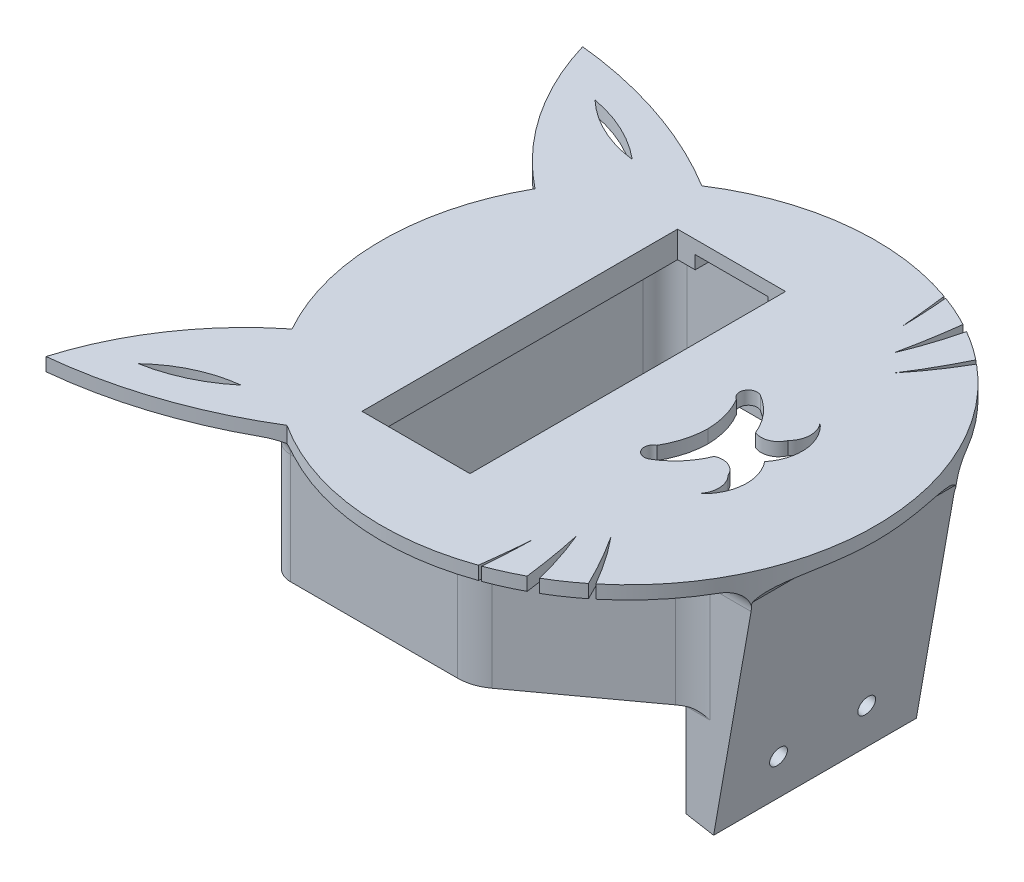
SolidWorks part; units mm, degrees
ref_plane "Front Plane" through (0, 0, 0) normal (0, 0, 1) x (1, 0, 0)
ref_plane "Top Plane" through (0, 0, 0) normal (0, 1, 0) x (1, 0, 0)
ref_plane "Right Plane" through (0, 0, 0) normal (1, 0, 0) x (0, 0, -1)
sketch "Sketch3" plane through (0, 0, 0) normal (0, 1, 0) x (1, 0, 0)
  line L0 (-100, 0) -> (0, 0) construction
  line L2 (-48.8284, -35.8) -> (-24.3284, -35.8)
  line L3 (-48.8284, -35.8) -> (-48.8284, 35.8)
  line L4 (-48.8284, 35.8) -> (-24.3284, 35.8)
  line L5 (-24.3284, -35.8) -> (-24.3284, 35.8)
  line L6 (-48.8284, -35.8) -> (-24.3284, 35.8) construction
  line L7 (-48.8284, 35.8) -> (-24.3284, -35.8) construction
  circle A0 centre (-24.1215, 0) radius 56.0598
  arc A1 (-54.5886, -47.058) -> (-95.4475, -60.8804) centre (-105.4462, 35.9761) cw
  arc A2 (-95.4475, -60.8804) -> (-72.9377, -27.5623) centre (-31.2759, -79.972) cw
  arc A3 (-54.5886, 47.058) -> (-95.4475, 60.8804) centre (-105.4462, -35.9761) ccw
  arc A4 (-95.4475, 60.8804) -> (-72.9377, 27.5623) centre (-31.2759, 79.972) ccw
  arc A5 (-6.1696, 0) -> (-8.7065, 9.0222) centre (-24.4857, -0.2825) ccw
  arc A6 (-8.7065, 9.0222) -> (-6.8513, 12.5893) centre (-7.7789, 10.8058) cw
  arc A7 (-6.8513, 12.5893) -> (0, 4.6761) centre (-15.0294, -1.4138) cw
  arc A8 (0, 4.6761) -> (5.2387, 6.7988) centre (1.558, 8.3568) ccw
  arc A9 (5.2387, 6.7988) -> (5.2387, 14.0413) centre (1.6175, 10.4201) ccw
  arc A10 (5.2387, 14.0413) -> (6.7387, 0) centre (-1.032, 6.2707) cw
  arc A11 (0, -4.6761) -> (5.2387, -6.7988) centre (1.558, -8.3568) cw
  arc A12 (5.2387, -6.7988) -> (5.2387, -14.0413) centre (1.6175, -10.4201) cw
  arc A13 (-6.8513, -12.5893) -> (0, -4.6761) centre (-15.0294, 1.4138) ccw
  arc A14 (-8.7065, -9.0222) -> (-6.8513, -12.5893) centre (-7.7789, -10.8058) ccw
  arc A15 (-6.1696, 0) -> (-8.7065, -9.0222) centre (-24.4857, 0.2825) cw
  arc A16 (5.2387, -14.0413) -> (6.7387, 0) centre (-1.032, -6.2707) ccw
  arc A17 (-4.2521, 42.0799) -> (-18.8641, 106.2073) centre (-236.5807, 22.8701) ccw
  arc A18 (-18.8641, 106.2073) -> (-4.2521, 42.0799) centre (-168.4211, 38.4009) cw
  arc A19 (0, 36) -> (-1.032, 103.0638) centre (-143.6963, 67.3287) ccw
  arc A20 (-1.032, 103.0638) -> (0, 36) centre (-77.2813, 68.3507) cw
  arc A21 (4.0199, 32.1345) -> (21.5381, 91.1561) centre (-86.4358, 91.0932) ccw
  arc A22 (21.5381, 91.1561) -> (4.0199, 32.1345) centre (-57.6041, 82.5357) cw
  arc A23 (4.0199, -32.1345) -> (21.5381, -91.1561) centre (-86.4358, -91.0932) cw
  arc A24 (-1.032, -103.0638) -> (0, -36) centre (-77.2813, -68.3507) ccw
  arc A25 (0, -36) -> (-1.032, -103.0638) centre (-143.6963, -67.3287) cw
  arc A26 (-18.8641, -106.2073) -> (-4.2521, -42.0799) centre (-168.4211, -38.4009) ccw
  arc A27 (-4.2521, -42.0799) -> (-18.8641, -106.2073) centre (-236.5807, -22.8701) cw
  arc A28 (21.5381, -91.1561) -> (4.0199, -32.1345) centre (-57.6041, -82.5357) ccw
  arc A29 (-83.5713, 51.8155) -> (-67.669, 44.359) centre (-89.6943, 18.0714) cw
  arc A30 (-83.5713, 51.8155) -> (-67.669, 44.359) centre (-64.4592, 71.8903) ccw
  arc A31 (-83.5713, -51.8155) -> (-67.669, -44.359) centre (-89.6943, -18.0714) ccw
  arc A32 (-83.5713, -51.8155) -> (-67.669, -44.359) centre (-64.4592, -71.8903) cw
  point P3 (-36.5784, 0)
  dimension "D1" = 71.6
  dimension "D2" = 24.5
  dimension "D3" = 100
extrude "Boss-Extrude1" add sketch "Sketch3" along normal blind 3 contours A0 L5 L2 L3 L4 | A3 A4 A0 | A2 A1 A0
sketch "Sketch9" plane through (0, 0, 0) normal (0, -1, 0) x (1, 0, 0)
  line L0 (-48.8284, 35.8) -> (-24.3284, 35.8)
  line L1 (-24.3284, 35.8) -> (-24.3284, -35.8)
  line L2 (-24.3284, -35.8) -> (-28.3284, -35.8)
  line L3 (-48.8284, -35.8) -> (-24.3284, -35.8) construction
  line L4 (-28.3284, -35.8) -> (-28.3284, -40.8)
  line L5 (-28.3284, -40.8) -> (-19.3284, -40.8)
  line L6 (-19.3284, -40.8) -> (-19.3284, 40.8)
  line L7 (-19.3284, 40.8) -> (-53.8284, 40.8)
  line L8 (-53.8284, 40.8) -> (-53.8284, 34.8)
  line L9 (-53.8284, 34.8) -> (-50.8284, 34.8)
  line L10 (-50.8284, 34.8) -> (-50.8284, -10.8)
  line L11 (-50.8284, -10.8) -> (-53.8284, -10.8)
  line L12 (-53.8284, -10.8) -> (-53.8284, -40.8)
  line L13 (-53.8284, -40.8) -> (-44.8284, -40.8)
  line L14 (-44.8284, -40.8) -> (-44.8284, -35.8)
  line L15 (-44.8284, -35.8) -> (-48.8284, -35.8)
  line L16 (-48.8284, -35.8) -> (-48.8284, 35.8)
  line L17 (-24.3284, 35.8) -> (-24.3284, -35.8)
  line M53 (-24.3284, 35.8) -> (-24.3284, -35.8)
  line M54 (-24.3284, -35.8) -> (-48.8284, -35.8)
  line M55 (-48.8284, -35.8) -> (-48.8284, 35.8)
  line M56 (-48.8284, 35.8) -> (-24.3284, 35.8)
  dimension "D1" = 4
  dimension "D2" = 5
  dimension "D3" = 5
  dimension "D4" = 25
  dimension "D5" = 2
  dimension "D6" = 1
  dimension "D7" = 5
extrude "Boss-Extrude2" add sketch "Sketch9" along normal blind 3 contours L13 L14 L4 L5 L6 L7 L8 L9 L10 L11 L12 M54 M55 M56 M53
sketch "Sketch10" plane through (0, 0, 0) normal (0, -1, 0) x (1, 0, 0)
  line L0 (-80.1813, 0) -> (31.9383, 0) construction
  line L3 (-23.9972, -23) -> (27.0028, -23)
  line L4 (-23.9972, -23) -> (-23.9972, 23)
  line L5 (-23.9972, 23) -> (27.0028, 23)
  line L6 (27.0028, -23) -> (27.0028, 23)
  line L7 (-23.9972, -23) -> (27.0028, 23) construction
  line L8 (-23.9972, 23) -> (27.0028, -23) construction
  line L9 (-10.9312, -14.4635) -> (13.9368, -14.4635)
  line L10 (-10.9312, -14.4635) -> (-10.9312, 14.4635)
  line L11 (-10.9312, 14.4635) -> (13.9368, 14.4635)
  line L12 (13.9368, -14.4635) -> (13.9368, 14.4635)
  line L13 (-10.9312, -14.4635) -> (13.9368, 14.4635) construction
  line L14 (-10.9312, 14.4635) -> (13.9368, -14.4635) construction
  arc A0 (-72.9377, 27.5623) -> (-72.9377, -27.5623) centre (-24.1215, 0) ccw construction
  arc A1 (11.6083, -43.1981) -> (11.6083, 43.1981) centre (-24.1215, 0) ccw construction
  point P9 (1.5028, 0)
  point P10 (1.5028, 0)
  dimension "D1" = 46
  dimension "D2" = 51
extrude "Boss-Extrude3" add sketch "Sketch10" along normal blind 3
ref_plane "Plane1" through (26.7016, -4.7082, 0) normal (0.9848, -0.1736, 0) x (0, 0, 1)
sketch "Sketch11" plane through (26.7016, -4.7082, 0) normal (0.9848, -0.1736, 0) x (0, 0, 1)
  line L0 (-23, -1.7346) -> (23, -1.7346)
  line L1 (23, -1.7346) -> (23, 49.2654)
  line L2 (23, 49.2654) -> (-23, 49.2654)
  line L3 (-23, 49.2654) -> (-23, -1.7346)
  line L4 (0, 48.4772) -> (0, -1.7346) construction
  circle A0 centre (-10, 39.2654) radius 2
  circle A1 centre (10, 39.2654) radius 2
  dimension "D2" = 4
  dimension "D1" = 51
  dimension "D3" = 10
  dimension "D4" = 10
extrude "Boss-Extrude4" add sketch "Sketch11" against normal blind 5
sketch "Sketch13" plane through (0, -3, 0) normal (0, -1, 0) x (1, 0, 0)
  line L0 (13.9368, 14.4635) -> (13.9368, 23)
  line L1 (21.9257, 23) -> (-19.3284, 23) construction
  line L2 (13.9368, 23) -> (21.9257, 23)
  line L3 (21.9257, 23) -> (21.9257, -23)
  line L4 (21.9257, -23) -> (21.9257, 23) construction
  line L5 (21.9257, -23) -> (13.9368, -23)
  line L6 (-19.3284, -23) -> (21.9257, -23) construction
  line L7 (13.9368, -23) -> (13.9368, -14.4635)
  line L8 (13.9368, -14.4635) -> (13.9368, 14.4635)
extrude "Boss-Extrude5" add sketch "Sketch13" along normal blind 27
sketch "Sketch16" plane through (0, -30, 0) normal (0, -1, 0) x (1, 0, 0)
  line L0 (17.1649, 23) -> (13.9368, 23)
  line L1 (13.9368, 23) -> (13.9368, -23)
  line L2 (13.9368, -23) -> (17.1649, -23)
  line L3 (17.1649, -23) -> (17.1649, 23.2709)
  line M1 (13.9368, -23) -> (17.1649, -23)
  line M2 (17.1649, -23) -> (17.1649, 23)
  line M3 (17.1649, 23) -> (13.9368, 23)
  line M4 (13.9368, 23) -> (13.9368, -23)
extrude "Boss-Extrude6" [suppressed] add sketch "Sketch16" along normal blind 9 draft 10 contours M4 M1 M2 M3
sketch "Sketch17" plane through (0, 0, 0) normal (0, -1, 0) x (1, 0, 0)
  line L0 (-80.1813, 0) -> (31.9383, 0) construction
  line L2 (-19.4509, -40.8) -> (-56.6775, -40.8)
  line L3 (-28.3284, -40.8) -> (-19.3284, -40.8) construction
  line L4 (-56.6775, -40.8) -> (-56.6775, 40.8)
  line L5 (-56.6775, 0) -> (-73.3467, 0)
  line L6 (-73.3467, 0) -> (-60.1571, -44.4025)
  line L7 (-60.1571, -44.4025) -> (-15.3287, -44.4025)
  line L8 (-15.3287, -44.4025) -> (14.0672, -23)
  line L9 (-19.3284, -23) -> (27.0028, -23) construction
  line L10 (14.0672, -23) -> (-15.3287, -23)
  line L11 (-15.3287, -23) -> (-15.3287, -40.8)
  line L12 (-15.3287, -40.8) -> (-19.4509, -40.8)
  line L13 (-56.6775, -40.8) -> (-19.4509, -40.8)
  line L14 (-15.3287, -23) -> (14.0672, -23)
  line L15 (-19.4509, 40.8) -> (-56.6775, 40.8)
  line L16 (-15.3287, 40.8) -> (-19.4509, 40.8)
  line L17 (-15.3287, 23) -> (-15.3287, 40.8)
  line L18 (14.0672, 23) -> (-15.3287, 23)
  line L19 (-15.3287, 44.4025) -> (14.0672, 23)
  line L20 (-60.1571, 44.4025) -> (-15.3287, 44.4025)
  line L21 (-73.3467, 0) -> (-60.1571, 44.4025)
  arc A0 (-72.9377, 27.5623) -> (-72.9377, -27.5623) centre (-24.1215, 0) ccw construction
  arc A1 (27.0028, -23) -> (27.0028, 23) centre (-24.1215, 0) ccw construction
  line M14 (-19.3284, 23) -> (27.0028, 23)
  line M40 (27.0028, -23) -> (-19.3284, -23)
  line M42 (-19.3284, -40.8) -> (-28.3284, -40.8)
  line M46 (-44.8284, -40.8) -> (-53.8284, -40.8)
  line M52 (-53.8284, 40.8) -> (-19.3284, 40.8)
extrude "Boss-Extrude7" add sketch "Sketch17" along normal blind 30 contours L11 L12 L2 L4 L5 L6 L7 L8 M42 M46 M40 | L21 L5 L4 L15 L16 L17 L19 L20 M52 M14
fillet "Fillet4" radius 20 1 edges at (-73.3467, -15, 0)
fillet "Fillet5" radius 5 2 edges at (-60.1571, -15, -44.4025) (-60.1571, -15, 44.4025)
fillet "Fillet6" radius 10 2 edges at (-15.3287, -15, 44.4025) (-15.3287, -15, -44.4025)
sketch "Sketch24" [suppressed] plane through (21.7776, -3.84, 0) normal (-0.9848, 0.1736, 0) x (0, 0, 1)
  line L0 (23, -49.2654) -> (-23, -49.2654)
  line L1 (-23, -49.2654) -> (-23, -26.5636)
  line L2 (-23, -26.5636) -> (23, -26.5636)
  line L3 (23, -26.5636) -> (23, -49.2654)
sketch "Sketch25" plane through (0, -30, 0) normal (0, -1, 0) x (1, 0, 0)
sketch "Sketch46" plane through (0, -30, 0) normal (0, -1, 0) x (1, 0, 0)
  line L0 (17.1649, -23) -> (17.1649, 23)
  line L1 (17.1649, 23) -> (15.6649, 23)
  line L2 (17.1649, 23) -> (14.0672, 23) construction
  line L3 (15.6649, 23) -> (15.6649, -23)
  line L4 (14.0672, -23) -> (17.1649, -23) construction
  line L5 (15.6649, -23) -> (17.1649, -23)
  dimension "D1" = 1.5
extrude "Boss-Extrude10" add sketch "Sketch46" along normal up to surface (8.5069 mm away)
sketch "Sketch47" plane through (0, 0, 0) normal (0, -1, 0) x (1, 0, 0)
  line L0 (13.9368, 14.4635) -> (13.9368, -14.4635)
  line L1 (13.9368, -14.4635) -> (11.9368, -14.4635)
  line L2 (-10.9312, -14.4635) -> (13.9368, -14.4635) construction
  line L3 (11.9368, -14.4635) -> (11.9368, 14.4635)
  line L4 (13.9368, 14.4635) -> (-10.9312, 14.4635) construction
  line L5 (11.9368, 14.4635) -> (13.9368, 14.4635)
  dimension "D1" = 2
extrude "Boss-Extrude11" add sketch "Sketch47" along normal up to surface (3 mm away)
sketch "Sketch48" plane through (0, -3, 0) normal (0, -1, 0) x (1, 0, 0)
  line L0 (13.9368, 23) -> (13.9368, -23)
  line L1 (13.9368, -23) -> (11.9368, -23)
  line L2 (-15.3287, -23) -> (13.9368, -23) construction
  line L3 (11.9368, -23) -> (11.9368, 23)
  line L4 (13.9368, 23) -> (-15.3287, 23) construction
  line L5 (11.9368, 23) -> (13.9368, 23)
extrude "Boss-Extrude12" add sketch "Sketch48" along normal up to surface (27 mm away) up to face at (-18.3495, -30, 0)
sketch "Sketch49" plane through (0, -30, 0) normal (0, -1, 0) x (1, 0, 0)
  line L0 (15.6649, 23) -> (11.9368, 23)
  line L1 (11.9368, 23) -> (11.9368, -23)
  line L2 (11.9368, -23) -> (15.6649, -23)
  line L3 (15.6649, -23) -> (15.6649, 23)
extrude "Boss-Extrude13" add sketch "Sketch49" along normal up to surface (22.1302 mm away)
sketch "Sketch50" plane through (15.6649, 0, 0) normal (1, 0, 0) x (0, 0, -1)
  circle A0 centre (10, -42.6333) radius 2.0309
extrude "Cut-Extrude1" cut sketch "Sketch50" against normal up to surface (3.728 mm away) up to face at (11.9368, -17.626, 0)
sketch "Sketch52" plane through (15.6649, 0, 0) normal (1, 0, 0) x (0, 0, -1)
  circle A0 centre (-10, -42.6333) radius 2.0309
extrude "Cut-Extrude2" cut sketch "Sketch52" against normal up to surface (3.728 mm away) up to face at (11.9368, -42.6333, -12.0309)
sketch "Sketch54" plane through (26.7016, -4.7082, 0) normal (0.9848, -0.1736, 0) x (0, 0, -1)
  circle A0 centre (10, -39.2654) radius 2
  circle A1 centre (-10, -39.2654) radius 2
extrude "Cut-Extrude-Thin6" cut sketch "Sketch54" along normal up to surface (4.069 mm away) from offset 4 thin
sketch "Sketch56" plane through (0, -3, 0) normal (0, -1, 0) x (1, 0, 0)
  line L0 (-24.3284, 0) -> (-48.8284, 0) construction
  line L1 (-24.3284, 35.8) -> (-24.3284, -35.8) construction
  line L2 (-48.8284, -35.8) -> (-48.8284, 35.8) construction
  line L3 (-36.5784, 35.8) -> (-36.5784, -35.5434) construction
  line L4 (-48.8284, 35.8) -> (-24.3284, 35.8) construction
  circle A0 centre (-52.0784, -37.5) radius 0.6
  circle A1 centre (-21.0784, -37.5) radius 0.6
  circle A2 centre (-21.0784, 37.5) radius 0.6
  circle A3 centre (-52.0784, 37.5) radius 0.6
  dimension "D3" = 1.2
  dimension "D1" = 37.5
  dimension "D2" = 15.5
extrude "Cut-Extrude3" cut sketch "Sketch56" against normal blind 4
sketch "Sketch57" plane through (0, 0, 0) normal (0, -1, 0) x (1, 0, 0)
  line L0 (-19.3284, 23) -> (-15.3287, 23)
  line L1 (-15.3287, 23) -> (-19.3284, 23) construction
  line L2 (-15.3287, 23) -> (-15.3287, 40.8)
  line L3 (-15.3287, 40.8) -> (-19.3284, 40.8)
  line L4 (-19.3284, 40.8) -> (-19.3284, 23)
extrude "Boss-Extrude14" add sketch "Sketch57" along normal up to surface (3 mm away) up to face at (-21.0784, -3, -36.9)
sketch "Sketch58" plane through (0, 0, 0) normal (0, -1, 0) x (1, 0, 0)
  line L0 (-15.3287, -40.8) -> (-19.3284, -40.8)
  line L1 (-19.3284, -40.8) -> (-19.3284, -23)
  line L2 (-19.3284, -23) -> (-15.3287, -23)
  line L3 (-15.3287, -23) -> (-15.3287, -40.8)
extrude "Boss-Extrude15" add sketch "Sketch58" along normal up to surface (3 mm away) up to face at (-21.0784, -3, -36.9)
sketch "Sketch59" plane through (0, 0, 0) normal (0, -1, 0) x (1, 0, 0)
  line L0 (-56.6775, -40.8) -> (-56.6775, 40.8)
  line L1 (-56.6775, 40.8) -> (-53.8284, 40.8)
  line L2 (-53.8284, 40.8) -> (-53.8284, -40.8)
  line L3 (-53.8284, -40.8) -> (-56.6775, -40.8)
extrude "Boss-Extrude16" add sketch "Sketch59" along normal up to surface (3 mm away) up to face at (-26.8761, -3, -4.3833)
fillet "Fillet7" radius 10 2 edges at (14.0672, -15, 23) (14.0672, -15, -23)
fillet "Fillet8" radius 10 4 edges at (-15.3287, -16.5, -23) (-15.3287, -16.5, 23) (11.9368, -16.5, -23) (11.9368, -16.5, 23)
fillet "Fillet9" radius 5 4 edges at (-15.3287, -16.5, -40.8) (-56.6775, -16.5, -40.8) (-56.6775, -16.5, 40.8) (-15.3287, -16.5, 40.8)
ref_plane "Plane2" through (18.1468, -53.2252, 23) normal (-0.1736, -0.9848, 0) x (-0.9848, 0.1736, 0)
sketch "Sketch62" plane through (0, -30, 0) normal (0, -1, 0) x (1, 0, 0)
  line L0 (-72.483, 0) -> (-56.6775, 0) construction
  line L2 (-56.6775, -35.8) -> (-56.6775, 35.8) construction
  line L3 (-5.3287, 23) -> (-5.3287, 33) construction
  line L4 (-5.3287, -23) -> (-5.3287, -33) construction
  circle A1 centre (-64.5802, 0) radius 0.75
  arc A2 (-71.655, 5.695) -> (-71.655, -5.695) centre (-52.483, 0) ccw construction
  circle A3 centre (-5.3287, -28) radius 0.75
  circle A4 centre (-5.3287, 28) radius 0.75
  dimension "D1" = 1.5
  dimension "D2" = 1.5
  dimension "D3" = 1.5
extrude "Cut-Extrude4" cut sketch "Sketch62" against normal blind 20
fillet "Fillet10" radius 1 2 edges at (14.6294, -30, 23) (14.6294, -30, -23)
fillet "Fillet11" radius 5 15 edges at (22.1624, 0, 23) (-66.4372, 0, -23.2606) (-66.4372, 0, 23.2606) (-72.483, 0, 0) (-37.5049, 0, -44.4025) (-37.5049, 0, 44.4025) (-59.4165, 0, -43.4099) (-59.4165, 0, 43.4099) (-0.6308, 0, 33.7013) (-0.6308, 0, -33.7013) (-15.4885, 0, 43.9115) (-15.4885, 0, -43.9115) (22.1624, 0, -23) (14.227, 0, -23.491) (14.227, 0, 23.491)
fillet "Fillet12" radius 5 3 edges at (27.0028, 0, 0) (27.0028, -1.5, 23) (27.0028, -1.5, -23)
fillet "Fillet13" radius 5 3 edges at (0.449, -3, 14.4635) (-10.9312, -3, 0) (0.449, -3, -14.4635)
sketch "Sketch69" plane through (22.7624, -4.0136, 0) normal (-0.9848, 0.1736, 0) x (0, 0, 1)
  circle A0 centre (-10, -39.2654) radius 7
  circle A1 centre (10, -39.2654) radius 7
  dimension "D1" = 14
extrude "Cut-Extrude5" cut sketch "Sketch69" along normal up to next
